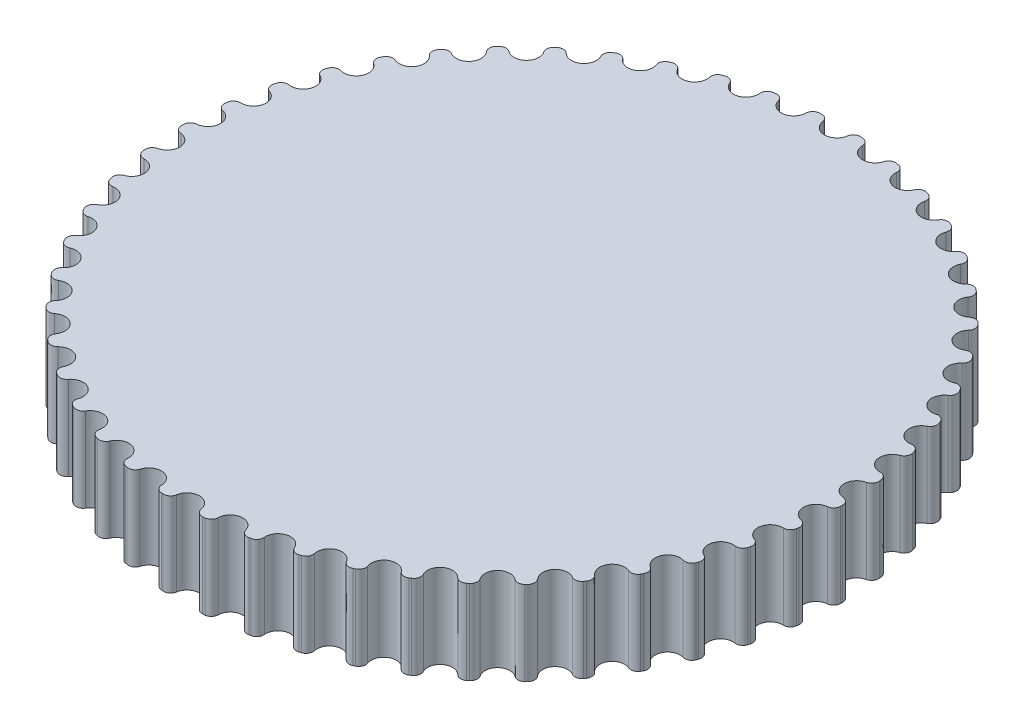
SolidWorks part; units mm, degrees
ref_plane "Front Plane" through (0, 0, 0) normal (0, 0, 1) x (1, 0, 0)
ref_plane "Top Plane" through (0, 0, 0) normal (0, 1, 0) x (1, 0, 0)
ref_plane "Right Plane" through (0, 0, 0) normal (1, 0, 0) x (0, 0, -1)
sketch "Sketch1" plane through (0, 0, 0) normal (0, 1, 0) x (1, 0, 0)
  line L0 (0, 0) -> (0, 23.4921) construction
  line L1 (0, 0) -> (2.903, 22.9795) construction
  circle A0 centre (0, 0) radius 23.4921 construction
  circle A1 centre (0, 0) radius 22.2721 construction
  circle A2 centre (0, 23.1621) radius 0.89 construction
  circle A5 centre (2.903, 22.9795) radius 0.89 construction
  arc A6 (0, 22.2721) -> (0.8797, 23.027) centre (0, 23.1621) ccw
  arc A7 (0.8797, 23.027) -> (1.4038, 23.4501) centre (1.3739, 22.951) cw
  arc A8 (1.5464, 23.4412) -> (2.0133, 22.9556) centre (1.5135, 22.9423) cw
  arc A9 (2.7914, 22.0965) -> (2.0133, 22.9556) centre (2.903, 22.9795) cw
  arc A10 (1.4038, 23.4501) -> (1.5464, 23.4412) centre (0, 0) cw
  arc A11 (0, 22.2721) -> (2.7914, 22.0965) centre (0, 0) ccw
  dimension "D1" = 46.9842
  dimension "D3" = 1.78
  dimension "D4" = 0.5
  dimension "D2" = 1.22
  dimension "D5" = 7.2
extrude "Boss-Extrude1" add sketch "Sketch1" along normal mid plane 6
ref_axis "Axis1" through (0, 3.3, 0) along (0, -1, 0)
pattern_circular "CirPattern1" count 50 over 360 about axis through (0, 3.3, 0) along (0, -1, 0) of "Boss-Extrude1"
equation "\"TEETH_NUM\"= 50"
equation "\"TOOTH_PITCH\" = 3mm"
equation "\"PITCH_LINE_OFFSET\" = .015in"
equation "\"DIAMETER_PER_GROOVE\" = .954925mm"
equation "\"PITCH_DIAMETER\"= \"TEETH_NUM\" * \"DIAMETER_PER_GROOVE\""
equation "\"OUTSIDE_DIAMETER\"= \"PITCH_DIAMETER\" - \"PITCH_LINE_OFFSET\" * 2"
equation "\"D1@Sketch1\"=\"OUTSIDE_DIAMETER\""
equation "\"TOOTH_HEIGHT\" = 1.22mm"
equation "\"D2@Sketch1\"=\"TOOTH_HEIGHT\""
equation "\"TOOTH_DIAMETER\" = 1.78mm"
equation "\"INTERNAL_RADIUS\" = .5mm"
equation "\"D3@Sketch1\"=\"TOOTH_DIAMETER\""
equation "\"D5@Sketch1\"=360 / \"TEETH_NUM\""
equation "\"D4@Sketch1\"=\"INTERNAL_RADIUS\""
equation "\"D1@CirPattern1\"=\"TEETH_NUM\""
